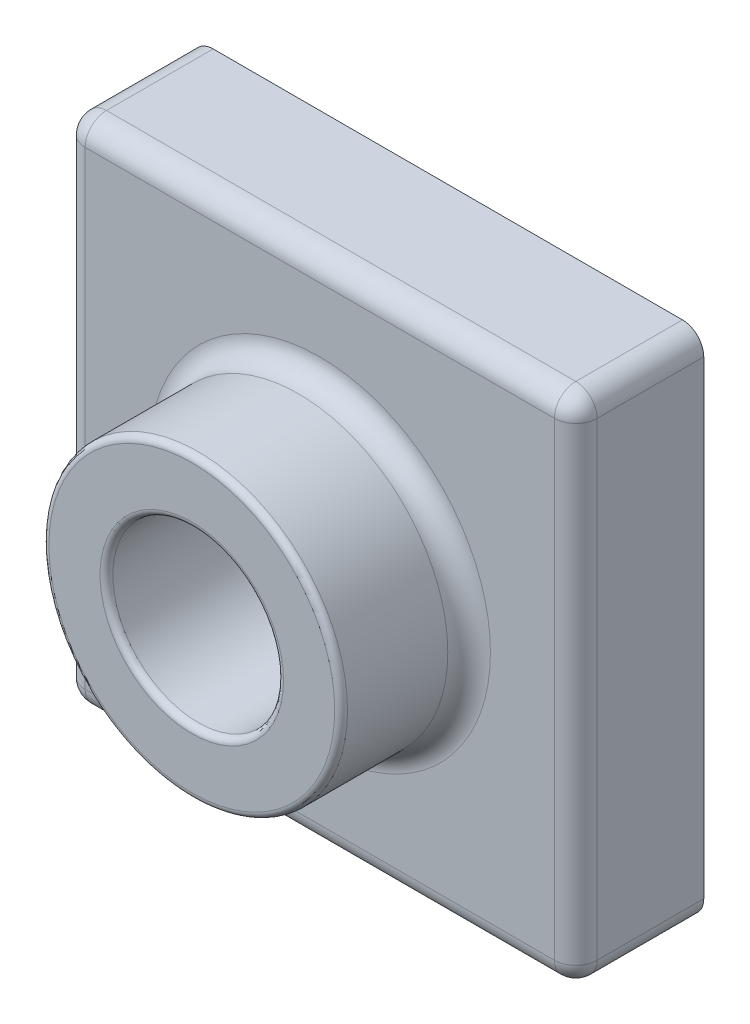
SolidWorks part; units mm, degrees
ref_plane "Front Plane" through (0, 0, 0) normal (0, 0, 1) x (1, 0, 0)
ref_plane "Top Plane" through (0, 0, 0) normal (0, 1, 0) x (1, 0, 0)
ref_plane "Right Plane" through (0, 0, 0) normal (1, 0, 0) x (0, 0, -1)
sketch "Sketch1" plane through (0, 0, 0) normal (0, 0, 1) x (1, 0, 0)
  line L1 (-60, 60) -> (60, 60)
  line L2 (-60, 60) -> (-60, -60)
  line L3 (-60, -60) -> (60, -60)
  line L4 (60, 60) -> (60, -60)
  line L5 (0, -60) -> (0, 60) construction
  line L6 (-60, 0) -> (60, 0) construction
  point P0 (0, 0)
  dimension "D1" = 120
  dimension "D2" = 120
extrude "Boss-Extrude1" add sketch "Sketch1" along normal blind 30
sketch "Sketch2" plane through (0, 0, 30) normal (0, 0, 1) x (1, 0, 0)
  circle A0 centre (0, 0) radius 35
  dimension "D1" = 70
extrude "Boss-Extrude3" add sketch "Sketch2" along normal blind 30
sketch "Sketch4" plane through (0, 0, 60) normal (0, 0, 1) x (1, 0, 0)
  circle A0 centre (0, 0) radius 20
extrude "Cut-Extrude2" cut sketch "Sketch4" against normal through all
fillet "Fillet1" radius 5 9 edges at (0, -60, 30) (-60, 0, 30) (0, 60, 30) (60, 0, 30) (35, 0, 30) (60, -60, 15) (-60, -60, 15) (-60, 60, 15) (60, 60, 15)
fillet "Fillet2" radius 1.5 3 edges at (20, 0, 60) (20, 0, 0) (35, 0, 60)
shell "Shell1" thickness 2 removed face at (21.5, 0, 0)
